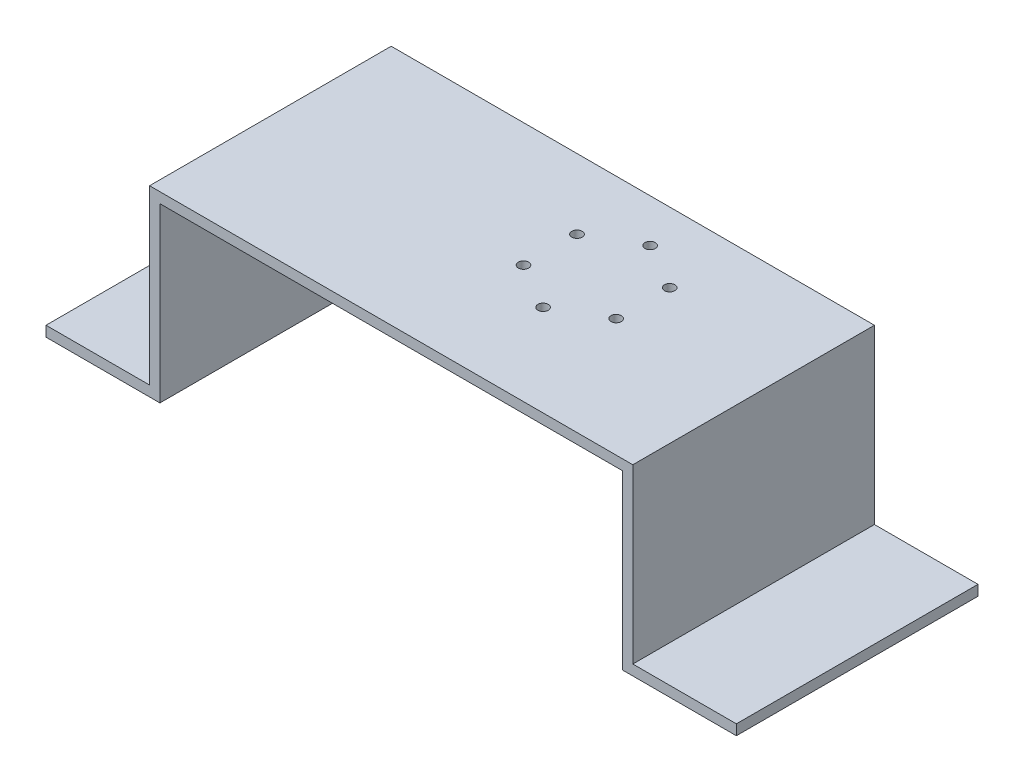
SolidWorks part; units mm, degrees
ref_plane "前视基准面" through (0, 0, 0) normal (0, 0, 1) x (1, 0, 0)
ref_plane "上视基准面" through (0, 0, 0) normal (0, 1, 0) x (1, 0, 0)
ref_plane "右视基准面" through (0, 0, 0) normal (1, 0, 0) x (0, 0, -1)
sketch "草图1" plane through (0, 0, 0) normal (0, 0, 1) x (1, 0, 0)
  line L0 (0, 0) -> (30, 0)
  line L1 (30, 0) -> (30, 50)
  line L2 (30, 50) -> (170, 50)
  line L3 (170, 50) -> (170, 0)
  line L4 (170, 0) -> (200, 0)
  line L5 (0, -3) -> (33, -3)
  line L6 (33, -3) -> (33, 47)
  line L7 (33, 47) -> (167, 47)
  line L8 (167, 47) -> (167, -3)
  line L9 (167, -3) -> (200, -3)
  line L10 (0, 0) -> (0, -3)
  line L11 (200, 0) -> (200, -3)
  dimension "D1" = 30
  dimension "D2" = 200
  dimension "D3" = 50
  dimension "D4" = 3
extrude "凸台-拉伸1" add sketch "草图1" along normal blind 70
sketch "草图2" plane through (0, 50, 0) normal (0, 1, 0) x (1, 0, 0)
  circle A0 centre (117.5021, -43.5) radius 1.5 construction
  circle A1 centre (130.9255, -35.75) radius 1.5 construction
  circle A2 centre (130.9255, -20.25) radius 1.5 construction
  circle A3 centre (117.5021, -12.5) radius 1.5 construction
  circle A4 centre (104.0787, -35.75) radius 1.5 construction
  circle A5 centre (104.0787, -20.25) radius 1.5 construction
  circle A6 centre (117.5021, -43.5) radius 1.5
  circle A7 centre (130.9255, -35.75) radius 1.5
  circle A8 centre (130.9255, -20.25) radius 1.5
  circle A9 centre (117.5021, -12.5) radius 1.5
  circle A10 centre (104.0787, -35.75) radius 1.5
  circle A11 centre (104.0787, -20.25) radius 1.5
extrude "切除-拉伸1" cut sketch "草图2" against normal blind 10
